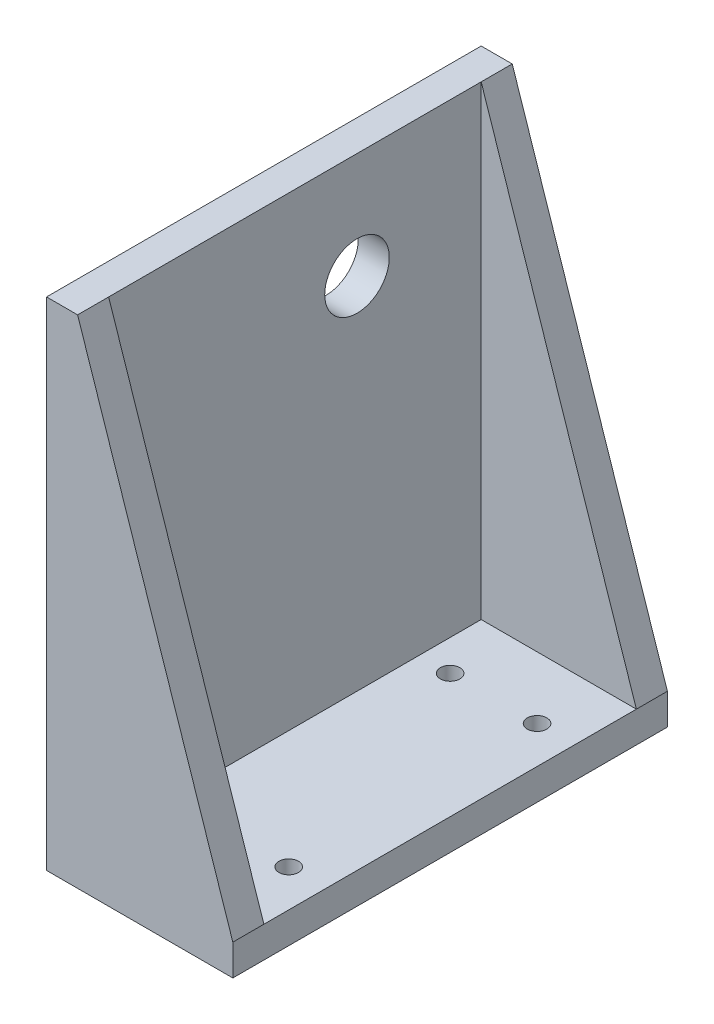
SolidWorks part; units mm, degrees
ref_plane "Front Plane" through (0, 0, 0) normal (0, 0, 1) x (1, 0, 0)
ref_plane "Top Plane" through (0, 0, 0) normal (0, 1, 0) x (1, 0, 0)
ref_plane "Right Plane" through (0, 0, 0) normal (1, 0, 0) x (0, 0, -1)
sketch "Sketch1" plane through (0, 0, 0) normal (0, 0, 1) x (1, 0, 0)
  line L0 (0, 0) -> (0, 50.8)
  line L1 (0, 50.8) -> (3.175, 50.8)
  line L2 (3.175, 50.8) -> (3.175, 3.175)
  line L3 (3.175, 3.175) -> (19.05, 3.175)
  line L4 (19.05, 3.175) -> (19.05, 0)
  line L5 (19.05, 0) -> (0, 0)
  dimension "D1" = 3.175
  dimension "D2" = 3.175
  dimension "D3" = 19.05
  dimension "D4" = 50.8
extrude "Boss-Extrude1" add sketch "Sketch1" along normal mid plane 44.45
sketch "Sketch2" plane through (0, 0, 0) normal (-1, 0, 0) x (0, 0, 1)
  line L1 (22.225, 50.8) -> (22.225, 0) construction
  line L2 (22.225, 0) -> (-22.225, 0) construction
  circle A0 centre (-6.35, 39.9542) radius 3.302
  dimension "D3" = 6.604
  dimension "D1" = 28.575
  dimension "D2" = 39.9542
sketch "Sketch3" plane through (0, 0, 22.225) normal (0, 0, 1) x (1, 0, 0)
  line L0 (3.175, 50.8) -> (19.05, 3.175)
  line L1 (19.05, 3.175) -> (3.175, 3.175)
  line L2 (3.175, 3.175) -> (3.175, 50.8)
extrude "Cut-Extrude1" cut sketch "Sketch2" against normal through all
extrude "Boss-Extrude2" add sketch "Sketch3" against normal blind 3.175
mirror "Mirror1" about plane through (0, 0, 0) normal (0, 0, 1) of "Boss-Extrude2"
sketch "Sketch4" plane through (0, 3.175, 0) normal (0, 1, 0) x (1, 0, 0)
  line L1 (3.175, 19.05) -> (19.05, 19.05) construction
  line L3 (3.175, 0) -> (19.05, 0) construction
  line L4 (3.175, -19.05) -> (3.175, 19.05) construction
  line L5 (19.05, -19.05) -> (19.05, 19.05) construction
  circle A0 centre (6.35, 12.7) radius 1
  circle A1 centre (15.24, 12.7) radius 1
  circle A2 centre (15.24, -12.7) radius 1
  circle A3 centre (6.35, -12.7) radius 1
  dimension "D1" = 2
  dimension "D2" = 6.35
  dimension "D3" = 3.175
  dimension "D5" = 8.89
  dimension "D4" = 2
extrude "Cut-Extrude2" cut sketch "Sketch4" against normal through all
equation "\"D1@Sketch4\"=2mm"
equation "\"tightTol\" = 0.005in"
equation "\"normTol\"= 0.01in"
equation "\"looseTol\"= 0.02in"
equation "\"D3@Sketch2\"=\"normTol\"+1/4"
